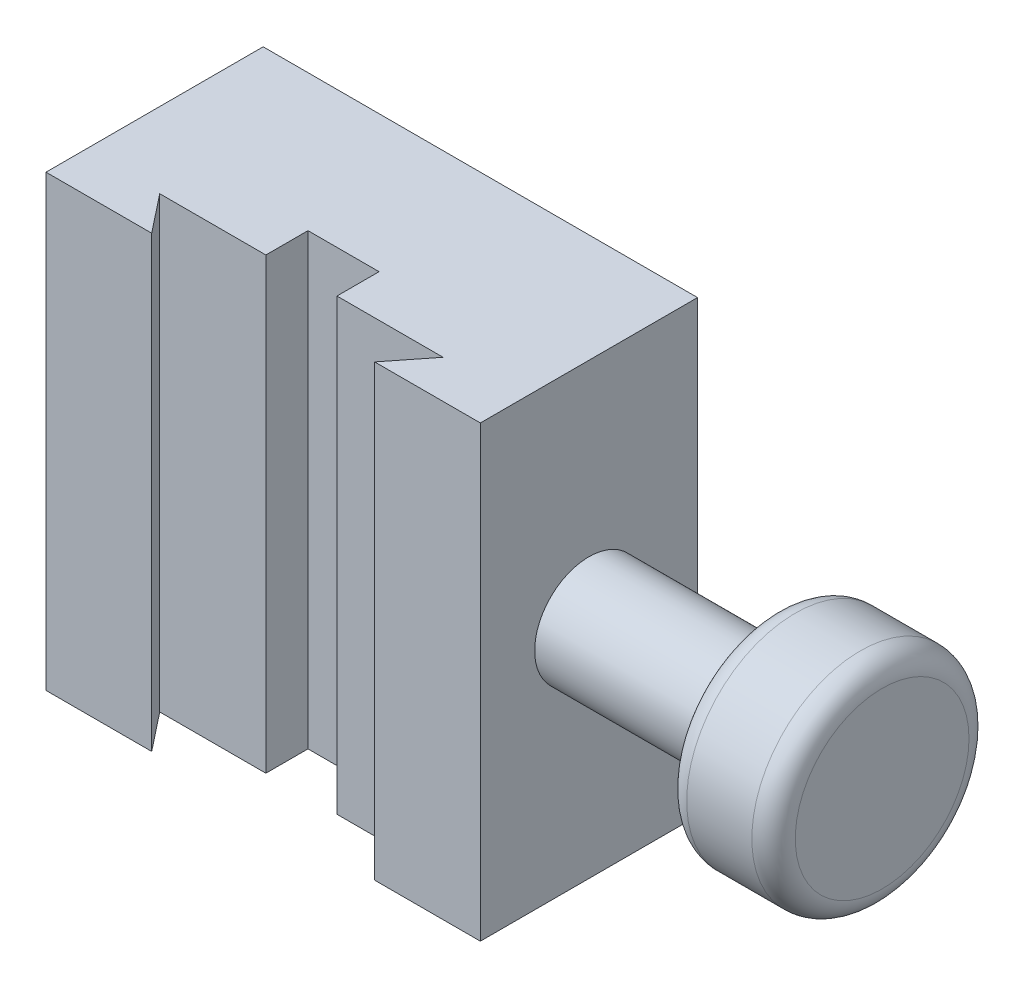
SolidWorks part; units mm, degrees
ref_plane "Front Plane" through (0, 0, 0) normal (0, 0, 1) x (1, 0, 0)
ref_plane "Top Plane" through (0, 0, 0) normal (0, 1, 0) x (1, 0, 0)
ref_plane "Right Plane" through (0, 0, 0) normal (1, 0, 0) x (0, 0, -1)
sketch "Sketch1" plane through (0, 0, 0) normal (0, 0, 1) x (1, 0, 0)
  line L0 (25.4, 34.2946) -> (25.4, -33.7298) construction
  line L1 (-30, -31) -> (30, -31)
  line L2 (-30, -31) -> (-30, 31)
  line L3 (-30, 31) -> (30, 31)
  line L4 (30, -31) -> (30, 31)
  line L5 (-30, -31) -> (30, 31) construction
  line L6 (-30, 31) -> (30, -31) construction
  line L7 (-39.9708, 25.4) -> (32.496, 25.4) construction
  line L8 (0, 44.2941) -> (0, -35.791) construction
  line L9 (-35.6727, 0) -> (42.6271, 0) construction
  line L10 (-12.7, 35.8775) -> (-12.7, -33.7506) construction
  line L11 (-35.6727, 12.7) -> (41.2243, 12.7) construction
  circle A0 centre (0, 0) radius 3.175
  circle A1 centre (25.4, 25.4) radius 3.175
  circle A2 centre (-25.4, 25.4) radius 3.175
  circle A3 centre (-25.4, -25.4) radius 3.175
  circle A4 centre (25.4, -25.4) radius 3.175
  circle A5 centre (-12.7, 12.7) radius 3.175
  circle A6 centre (12.7, 12.7) radius 3.175
  circle A7 centre (-12.7, -12.7) radius 3.175
  circle A8 centre (12.7, -12.7) radius 3.175
  point P0 (0, 0)
  dimension "D3" = 6.35
  dimension "D6" = 6.35
  dimension "D9" = 6.35
  dimension "D1" = 60
  dimension "D2" = 62
  dimension "D4" = 25.4
  dimension "D5" = 25.4
  dimension "D7" = 12.7
  dimension "D8" = 12.7
extrude "Boss-Extrude1" add sketch "Sketch1" along normal blind 30 contours L2 L1 L4 L3
sketch "Sketch3" plane through (30, 0, 0) normal (1, 0, 0) x (0, 0, -1)
  line L0 (-30, -31) -> (-30, 31) construction
  circle A0 centre (-15, 0) radius 7.5
  dimension "D1" = 15
  dimension "D2" = 15
extrude "Boss-Extrude2" add sketch "Sketch3" along normal blind 25.5
sketch "Sketch4" plane through (55.5, 0, 0) normal (1, 0, 0) x (0, 0, -1)
  circle A0 centre (-15, 0) radius 15
  dimension "D1" = 30
extrude "Boss-Extrude3" add sketch "Sketch4" along normal blind 15 contours A0
fillet "Fillet1" radius 3 2 edges at (55.5, 0, 0) (70.5, 0, 0)
extrude "Boss-Extrude4" add sketch "Sketch1<3>" along normal blind 20
sketch "Sketch1<3>" plane through (0, 0, 0) normal (0, 0, 1) x (1, 0, 0) same geometry as "Sketch1"
hole_wizard "1/4-20 Tapped Hole1" positions "Sketch12" profile "Sketch13" tap size "1/4-20" standard "ANSI Inch"
sketch "Sketch12" plane through (0, 0, 0) normal (0, 0, -1) x (-1, 0, 0)
  line L0 (0, 35.1031) -> (0, -34.9957) construction
  line L2 (-35.8319, 0) -> (32.6951, 0) construction
  point P0 (-25.4, 25.4)
  point P2 (25.4, 25.4)
  point P4 (25.4, -25.4)
  point P6 (-25.4, -25.4)
  dimension "D1" = 25.4
  dimension "D2" = 25.4
  dimension "D3" = 25.4
  dimension "D4" = 25.4
  dimension "D5" = 25.4
  dimension "D6" = 25.4
  dimension "D7" = 25.4
  dimension "D8" = 25.4
sketch "Sketch13" plane through (25.4, 25.4, 0) normal (1, 0, 0) x (0, 1, 0)
  line L0 (0, 0) -> (0, 18.0438)
  line L1 (0, 18.0438) -> (2.5527, 16.51)
  line L2 (2.5527, 16.51) -> (2.5527, 0)
  line L5 (2.5527, 0) -> (0, 0)
  line L10 (0, 18.0438) -> (-2.5527, 16.51) construction
  line L11 (0, -6.35) -> (0, 107.95) construction
  dimension "Tap Drill Dia." = 5.1054
  dimension "Tap Drill Depth" = 16.51
  dimension "Drill Angle" = 118
cosmetic thread "Hole Thread1" parameters "D1"=12.7, "D2"=6.35
cosmetic thread "Hole Thread2" parameters "D1"=12.7, "D2"=6.35
cosmetic thread "Hole Thread3" parameters "D1"=12.7, "D2"=6.35
cosmetic thread "Hole Thread4" parameters "D1"=12.7, "D2"=6.35
hole_wizard "1/4-20 Tapped Hole2" positions "Sketch14" profile "Sketch15" tap size "1/4-20" standard "ANSI Inch"
sketch "Sketch14" plane through (0, 0, 0) normal (0, 0, -1) x (-1, 0, 0)
  line L0 (0, 34.2753) -> (0, -36.515) construction
  line L2 (36.593, 0) -> (-33.9459, 0) construction
  point P0 (-12.7, 12.7)
  point P2 (0, 0)
  point P5 (12.7, 12.7)
  point P7 (12.7, -12.7)
  point P9 (-12.7, -12.7)
  dimension "D1" = 12.7
  dimension "D2" = 12.7
  dimension "D3" = 12.7
  dimension "D4" = 12.7
  dimension "D5" = 12.7
  dimension "D6" = 12.7
  dimension "D7" = 12.7
  dimension "D8" = 12.7
sketch "Sketch15" plane through (12.7, 12.7, 0) normal (1, 0, 0) x (0, 1, 0)
  line L0 (0, 0) -> (0, 18.0438)
  line L1 (0, 18.0438) -> (2.5527, 16.51)
  line L2 (2.5527, 16.51) -> (2.5527, 0)
  line L5 (2.5527, 0) -> (0, 0)
  line L10 (0, 18.0438) -> (-2.5527, 16.51) construction
  line L11 (0, -6.35) -> (0, 107.95) construction
  dimension "Tap Drill Dia." = 5.1054
  dimension "Tap Drill Depth" = 16.51
  dimension "Drill Angle" = 118
cosmetic thread "Hole Thread5" parameters "D1"=12.7, "D2"=6.35
cosmetic thread "Hole Thread6" parameters "D1"=12.7, "D2"=6.35
cosmetic thread "Hole Thread7" parameters "D1"=12.7, "D2"=6.35
cosmetic thread "Hole Thread8" parameters "D1"=12.7, "D2"=6.35
cosmetic thread "Hole Thread9" parameters "D1"=12.7, "D2"=6.35
sketch "Sketch16" plane through (0, -31, 0) normal (0, -1, 0) x (1, 0, 0)
  line L0 (0, -10.4479) -> (0, 35.4601) construction
  line L1 (-4.91, 24.72) -> (-19.57, 24.72)
  line L2 (4.91, 24.72) -> (-4.91, 24.72) construction
  line L3 (4.91, 24.72) -> (4.91, 18.9)
  line L4 (4.91, 18.9) -> (-4.91, 18.9)
  line L5 (-4.91, 24.72) -> (-4.91, 18.9)
  line L6 (4.91, 24.72) -> (-4.91, 18.9) construction
  line L7 (4.91, 18.9) -> (-4.91, 24.72) construction
  line L8 (4.91, 24.72) -> (19.57, 24.72)
  line L9 (-19.57, 24.72) -> (-15.4, 30)
  line L10 (-30, 30) -> (30, 30) construction
  line L11 (19.57, 24.72) -> (15.4, 30)
  line L12 (-15.4, 30) -> (15.4, 30)
  point P3 (0, 21.81)
  dimension "D1" = 9.82
  dimension "D2" = 5.82
  dimension "D3" = 11.1
  dimension "D4" = 19.57
  dimension "D5" = 15.4
extrude "Cut-Extrude1" cut sketch "Sketch16" against normal through all
